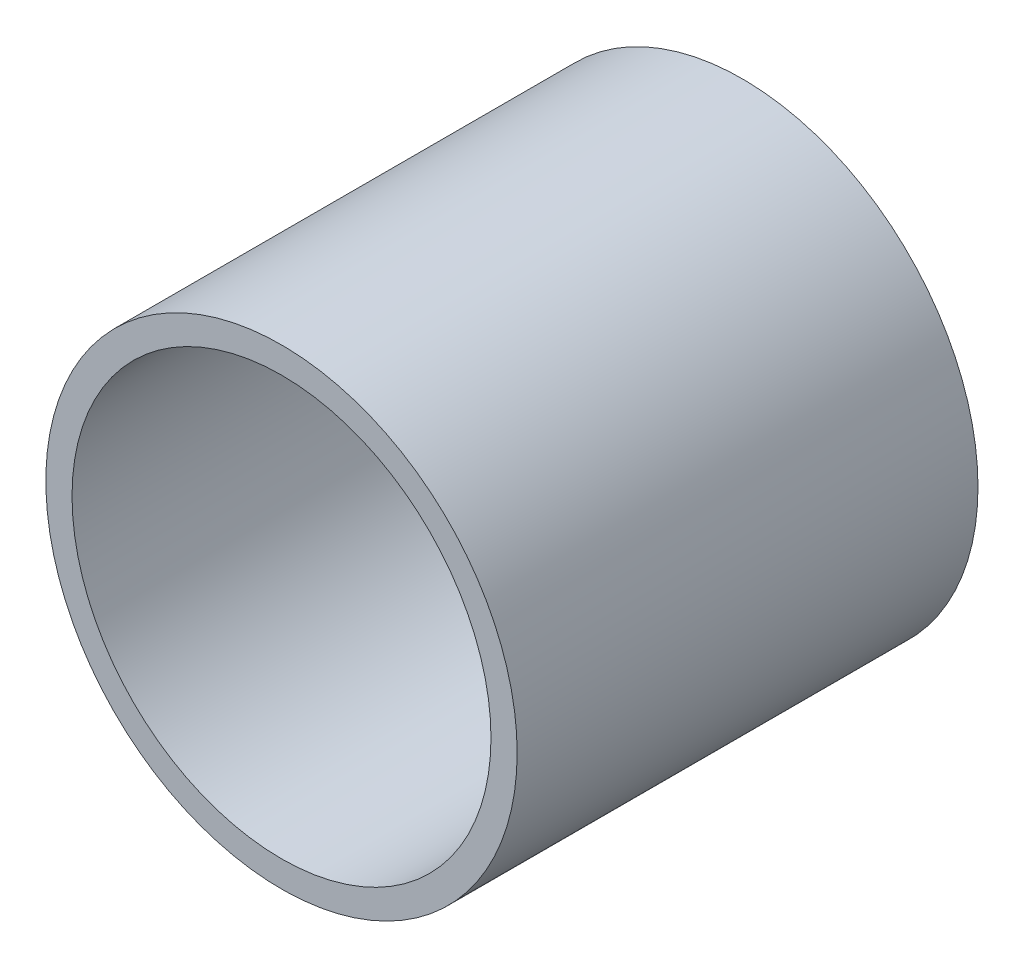
SolidWorks part; units mm, degrees
ref_plane "Front Plane" through (0, 0, 0) normal (0, 0, 1) x (1, 0, 0)
ref_plane "Top Plane" through (0, 0, 0) normal (0, 1, 0) x (1, 0, 0)
ref_plane "Right Plane" through (0, 0, 0) normal (1, 0, 0) x (0, 0, -1)
sketch "Sketch1" plane through (0, 0, 0) normal (0, 0, 1) x (1, 0, 0)
  circle A0 centre (0, 0) radius 7.1438
  dimension "D1" = 14.2875
extrude "Extrude1" add sketch "Sketch1" along normal blind 13.97
sketch "Sketch2" plane through (0, 0, 13.97) normal (0, 0, 1) x (1, 0, 0)
  circle A0 centre (0, 0) radius 6.35
  dimension "D1" = 12.7
extrude "Extrude2" cut sketch "Sketch2" against normal up to next
